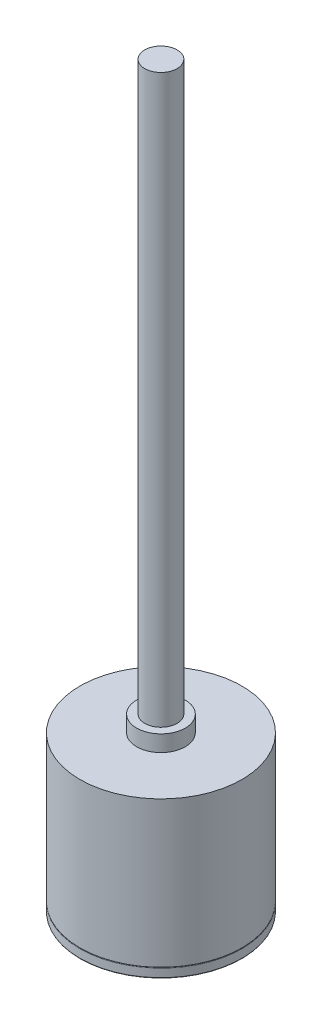
SolidWorks part; units mm, degrees
ref_plane "前视基准面" through (0, 0, 0) normal (0, 0, 1) x (1, 0, 0)
ref_plane "上视基准面" through (0, 0, 0) normal (0, 1, 0) x (1, 0, 0)
ref_plane "右视基准面" through (0, 0, 0) normal (1, 0, 0) x (0, 0, -1)
sketch "草图1" plane through (0, 0, 0) normal (0, 1, 0) x (1, 0, 0)
  circle A0 centre (0, 0) radius 5
  dimension "D1" = 10
extrude "凸台-拉伸1" add sketch "草图1" along normal blind 0.6
fillet "圆角1" radius 0.05 1 edges at (0, 0.6, 5)
fillet "圆角2" radius 0.05 1 edges at (0, 0, 5)
sketch "草图2" plane through (0, 0.6, 0) normal (0, 1, 0) x (1, 0, 0)
  circle A0 centre (0, 0) radius 5
extrude "凸台-拉伸2" add sketch "草图2" along normal blind 9
sketch "草图3" plane through (0, 9.6, 0) normal (0, 1, 0) x (1, 0, 0)
  circle A0 centre (0, 0) radius 1.5
  dimension "D1" = 3
extrude "凸台-拉伸3" add sketch "草图3" along normal blind 1
sketch "草图4" plane through (0, 10.6, 0) normal (0, 1, 0) x (1, 0, 0)
  circle A0 centre (0, 0) radius 1
  dimension "D1" = 2
extrude "凸台-拉伸4" add sketch "草图4" along normal blind 35
ref_axis "基准轴1" through (0, 9.6, 0) along (0, -1, 0)
